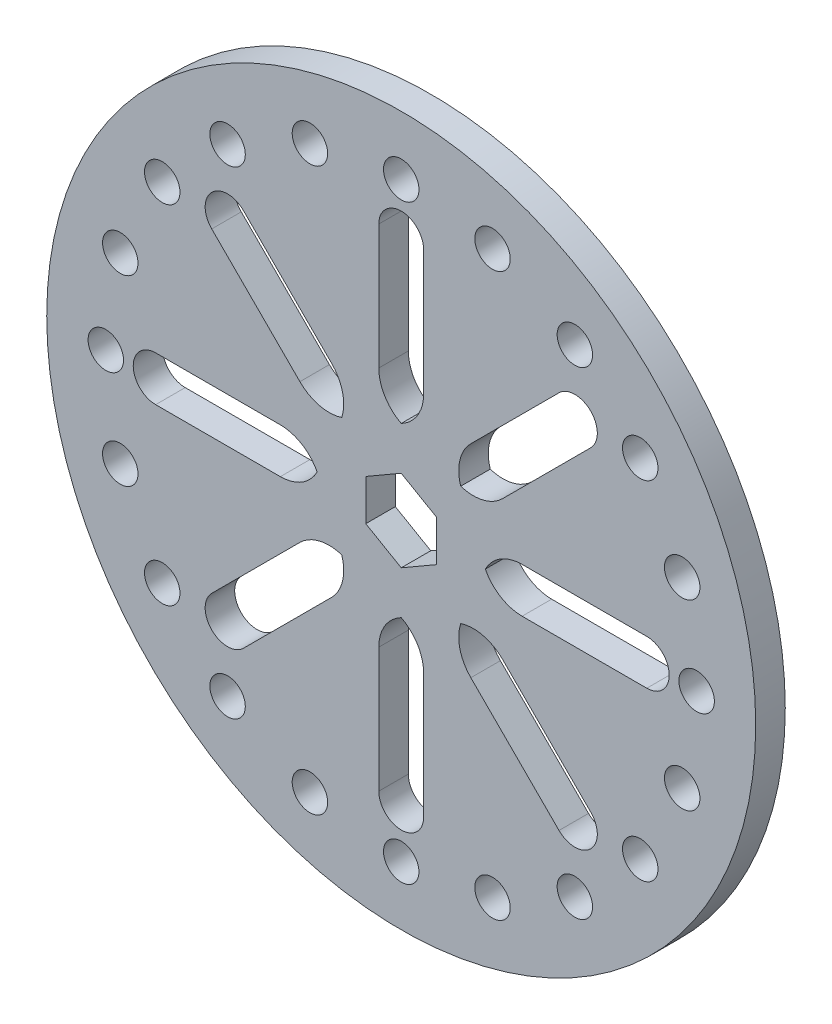
SolidWorks part; units mm, degrees
ref_plane "Front Plane" through (0, 0, 0) normal (0, 0, 1) x (1, 0, 0)
ref_plane "Top Plane" through (0, 0, 0) normal (0, 1, 0) x (1, 0, 0)
ref_plane "Right Plane" through (0, 0, 0) normal (1, 0, 0) x (0, 0, -1)
sketch "Sketch1" plane through (0, 0, 0) normal (0, 0, 1) x (1, 0, 0)
  circle A0 centre (0, 0) radius 60
  dimension "D1" = 120
extrude "Boss-Extrude1" add sketch "Sketch1" along normal blind 5
sketch "Sketch2" plane through (0, 0, 5) normal (0, 0, 1) x (1, 0, 0)
  line L0 (-29.3893, 29.3893) -> (-9.3127, 9.3127) construction
  line L1 (-26.7045, 32.074) -> (-6.6279, 11.9974)
  line L2 (-32.074, 26.7045) -> (-11.9974, 6.6279)
  line L3 (0, 41.5627) -> (0, 13.1701) construction
  line L4 (3.7968, 41.5627) -> (3.7968, 13.1701)
  line L5 (-3.7968, 41.5627) -> (-3.7968, 13.1701)
  line L6 (29.3893, 29.3893) -> (9.3127, 9.3127) construction
  line L7 (32.074, 26.7045) -> (11.9974, 6.6279)
  line L8 (26.7045, 32.074) -> (6.6279, 11.9974)
  line L9 (41.5627, 0) -> (13.1701, 0) construction
  line L10 (41.5627, -3.7968) -> (13.1701, -3.7968)
  line L11 (41.5627, 3.7968) -> (13.1701, 3.7968)
  line L12 (29.3893, -29.3893) -> (9.3127, -9.3127) construction
  line L13 (26.7045, -32.074) -> (6.6279, -11.9974)
  line L14 (32.074, -26.7045) -> (11.9974, -6.6279)
  line L15 (0, -41.5627) -> (0, -13.1701) construction
  line L16 (-3.7968, -41.5627) -> (-3.7968, -13.1701)
  line L17 (3.7968, -41.5627) -> (3.7968, -13.1701)
  line L18 (-29.3893, -29.3893) -> (-9.3127, -9.3127) construction
  line L19 (-32.074, -26.7045) -> (-11.9974, -6.6279)
  line L20 (-26.7045, -32.074) -> (-6.6279, -11.9974)
  line L21 (-41.5627, 0) -> (-13.1701, 0) construction
  line L22 (-41.5627, 3.7968) -> (-13.1701, 3.7968)
  line L23 (-41.5627, -3.7968) -> (-13.1701, -3.7968)
  circle A0 centre (0, 0) radius 2
  circle A1 centre (0, 0) radius 50 construction
  circle A2 centre (0, 50) radius 3
  circle A3 centre (15.4508, 47.5528) radius 3
  circle A4 centre (29.3893, 40.4508) radius 3
  circle A5 centre (40.4508, 29.3893) radius 3
  circle A6 centre (47.5528, 15.4508) radius 3
  circle A7 centre (50, 0) radius 3
  circle A8 centre (47.5528, -15.4508) radius 3
  circle A9 centre (40.4508, -29.3893) radius 3
  circle A10 centre (29.3893, -40.4508) radius 3
  circle A11 centre (15.4508, -47.5528) radius 3
  circle A12 centre (0, -50) radius 3
  circle A13 centre (-15.4508, -47.5528) radius 3
  circle A14 centre (-29.3893, -40.4508) radius 3
  circle A15 centre (-40.4508, -29.3893) radius 3
  circle A16 centre (-47.5528, -15.4508) radius 3
  circle A17 centre (-50, 0) radius 3
  circle A18 centre (-47.5528, 15.4508) radius 3
  circle A19 centre (-40.4508, 29.3893) radius 3
  circle A20 centre (-29.3893, 40.4508) radius 3
  circle A21 centre (-15.4508, 47.5528) radius 3
  arc A22 (-26.7045, 32.074) -> (-32.074, 26.7045) centre (-29.3893, 29.3893) ccw
  arc A24 (3.7968, 41.5627) -> (-3.7968, 41.5627) centre (0, 41.5627) ccw
  arc A26 (32.074, 26.7045) -> (26.7045, 32.074) centre (29.3893, 29.3893) ccw
  arc A28 (41.5627, -3.7968) -> (41.5627, 3.7968) centre (41.5627, 0) ccw
  arc A30 (26.7045, -32.074) -> (32.074, -26.7045) centre (29.3893, -29.3893) ccw
  arc A32 (-3.7968, -41.5627) -> (3.7968, -41.5627) centre (0, -41.5627) ccw
  arc A34 (-32.074, -26.7045) -> (-26.7045, -32.074) centre (-29.3893, -29.3893) ccw
  arc A36 (-41.5627, 3.7968) -> (-41.5627, -3.7968) centre (-41.5627, 0) ccw
  arc A38 (-13.1701, 3.7968) -> (-13.1701, -3.7968) centre (0, 0) ccw
  arc A39 (-6.6279, 11.9974) -> (-11.9974, 6.6279) centre (0, 0) ccw
  arc A40 (3.7968, 13.1701) -> (-3.7968, 13.1701) centre (0, 0) ccw
  arc A41 (11.9974, 6.6279) -> (6.6279, 11.9974) centre (0, 0) ccw
  arc A42 (13.1701, -3.7968) -> (13.1701, 3.7968) centre (0, 0) ccw
  arc A43 (6.6279, -11.9974) -> (11.9974, -6.6279) centre (0, 0) ccw
  arc A44 (-3.7968, -13.1701) -> (3.7968, -13.1701) centre (0, 0) ccw
  arc A45 (-11.9974, -6.6279) -> (-6.6279, -11.9974) centre (0, 0) ccw
  point P42 (0, 0)
  point P47 (-19.351, 19.351)
  point P56 (0, 27.3664)
  point P63 (19.351, 19.351)
  point P70 (27.3664, 0)
  point P77 (19.351, -19.351)
  point P84 (0, -27.3664)
  point P91 (-19.351, -19.351)
  point P98 (-27.3664, 0)
  point P103 (0, 0)
  dimension "D1" = 4
  dimension "D2" = 100
  dimension "D3" = 6
  dimension "D4" = 20
extrude "Cut-Extrude2" cut sketch "Sketch2" against normal blind 5
fillet "Fillet1" radius 7 16 edges at (11.9974, 6.6279, 2.5) (6.6279, 11.9974, 2.5) (13.1701, 3.7968, 2.5) (13.1701, -3.7968, 2.5) (11.9974, -6.6279, 2.5) (6.6279, -11.9974, 2.5) (3.7968, -13.1701, 2.5) (-3.7968, -13.1701, 2.5) (-6.6279, -11.9974, 2.5) (-11.9974, -6.6279, 2.5) (-13.1701, -3.7968, 2.5) (-13.1701, 3.7968, 2.5) (-6.6279, 11.9974, 2.5) (-11.9974, 6.6279, 2.5) (3.7968, 13.1701, 2.5) (-3.7968, 13.1701, 2.5)
sketch "Sketch3" plane through (0, 0, 5) normal (0, 0, 1) x (1, 0, 0)
  line L1 (0, 6.9282) -> (-6, 3.4641)
  line L2 (-6, 3.4641) -> (-6, -3.4641)
  line L3 (-6, -3.4641) -> (0, -6.9282)
  line L4 (0, -6.9282) -> (6, -3.4641)
  line L5 (6, -3.4641) -> (6, 3.4641)
  line L6 (6, 3.4641) -> (0, 6.9282)
  circle A0 centre (0, 0) radius 6 construction
  dimension "D1" = 12
  dimension "D2" = 6.9282
extrude "Cut-Extrude3" cut sketch "Sketch3" against normal blind 10
